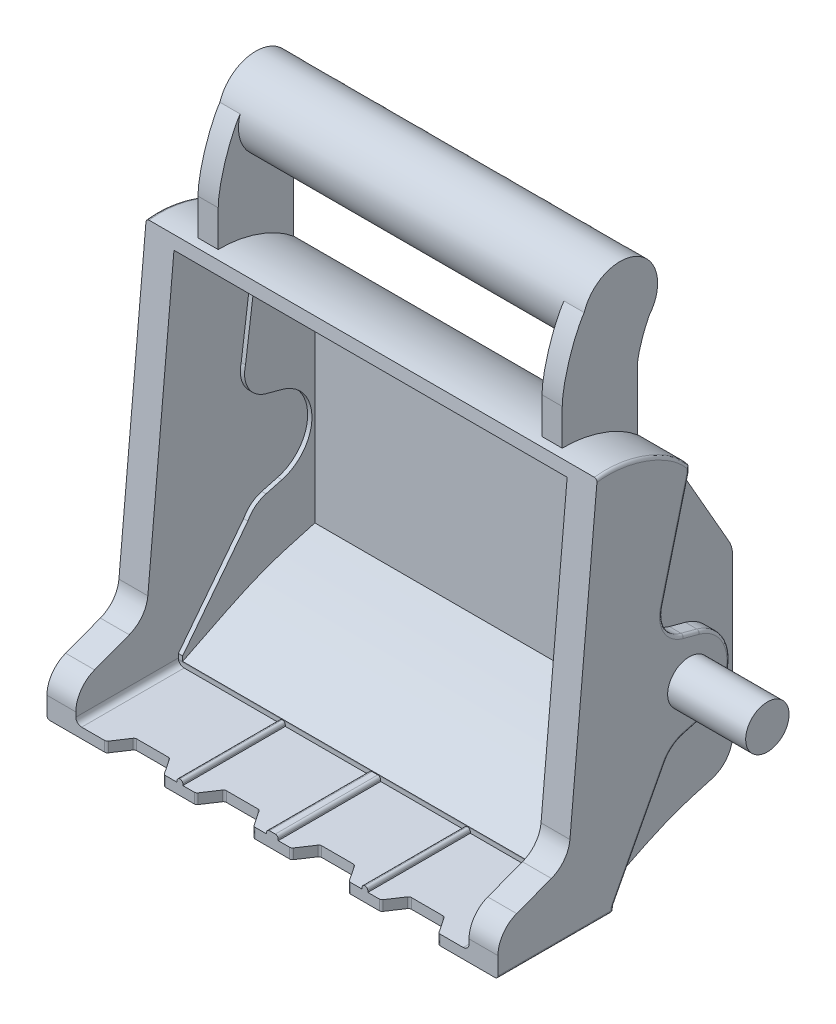
SolidWorks part; units mm, degrees
note: The reader was unsure of these and kept them because the rebuilt part matched: shared geometry of "Sketch1<8>", "Sketch6<3>", "Sketch10<4>", "Sketch10<5>", "Sketch11<4>".
material "PBT General Purpose"
ref_plane "Front Plane" through (0, 0, 0) normal (0, 0, 1) x (1, 0, 0)
ref_plane "Top Plane" through (0, 0, 0) normal (0, 1, 0) x (1, 0, 0)
ref_plane "Right Plane" through (0, 0, 0) normal (1, 0, 0) x (0, 0, -1)
sketch "Sketch1" plane through (0, 0, 0) normal (1, 0, 0) x (0, 0, -1)
  line L0 (0, 0) -> (-4.7154, -51.6541)
  line L1 (-7.9295, -55.8776) -> (-13.9281, -58.1411)
  line L2 (-17.1629, -62.8191) -> (-17.1629, -66.3617)
  line L3 (-17.1629, -66.3617) -> (2.8371, -66.3617)
  line L4 (2.8371, -66.3617) -> (2.9283, -65.3617)
  line L5 (25.9283, -56.3617) -> (25.9283, -24.3617)
  line L6 (25.9283, -24.3617) -> (16, -7)
  line L7 (16, -7) -> (16, -6)
  line L8 (2.2931, -2.38) -> (-2.2257, -51.8814)
  line L9 (-7.0469, -58.2167) -> (-13.0455, -60.4801)
  line L10 (-14.6629, -62.8191) -> (-14.6629, -63.8617)
  line L11 (-14.6629, -63.8617) -> (0.5549, -63.8617)
  line L12 (0.5549, -63.8617) -> (0.5649, -63.7517)
  line L13 (23.4283, -54.4401) -> (23.4283, -25.026)
  line L14 (23.4283, -25.026) -> (13.5, -7.6643)
  line L15 (13.5, -7.6643) -> (13.5, -6.9194)
  line L16 (-14.6629, -63.8617) -> (-17.1629, -63.8617)
  line L17 (2.2931, -2.38) -> (-0.1965, -2.1528)
  arc A0 (-4.7154, -51.6541) -> (-7.9295, -55.8776) centre (-9.6947, -51.1996) cw
  arc A1 (-13.9281, -58.1411) -> (-17.1629, -62.8191) centre (-12.1629, -62.8191) ccw
  arc A2 (-2.2257, -51.8814) -> (-7.0469, -58.2167) centre (-9.6947, -51.1996) cw
  arc A3 (-13.0455, -60.4801) -> (-14.6629, -62.8191) centre (-12.1629, -62.8191) ccw
  conic Q0 (2.9283, -65.3617) -> (25.9283, -56.3617) control (15.18, -59.202) rho 0.727082
  conic Q1 (16, -6) -> (0, 0) control (10.3278, 1.4347) rho 0.401111
  spline S0 degree 1 poles (13.5, -6.9194) (2.2931, -2.38) knots 0 0 1 1 construction
  spline S1 degree 1 poles (0.5649, -63.7517) (23.4283, -54.4401) knots 0 0 1 1 construction
  spline S2 degree 3 poles (13.5, -6.9194) (13.3729, -6.786) (13.1202, -6.5368) (12.5037, -5.9951) (11.5779, -5.3085) (10.2261, -4.5064) (8.6893, -3.7839) (7.04, -3.1852) (5.3626, -2.7418) (4.0174, -2.513) (3.0001, -2.4115) (2.5324, -2.3868) (2.2931, -2.38) knots 0.079459 0.079459 0.079459 0.079459 0.127453 0.175447 0.271436 0.367424 0.463412 0.5594 0.655388 0.751376 0.79937 0.847364 0.847364 0.847364 0.847364
  spline S3 degree 3 poles (0.5649, -63.7517) (1.2219, -63.4214) (2.6157, -62.7202) (4.2287, -61.9132) (5.5628, -61.2497) (7.0471, -60.5169) (8.5038, -59.8072) (9.873, -59.1546) (11.0033, -58.6305) (11.9816, -58.1918) (12.8652, -57.8113) (13.9719, -57.3563) (15.0367, -56.9517) (16.1815, -56.5528) (17.1182, -56.2449) (18.185, -55.9129) (19.2467, -55.5988) (20.2667, -55.3074) (21.1416, -55.0623) (21.9972, -54.8271) (22.7694, -54.6174) (23.2135, -54.4978) (23.4283, -54.4401) knots -0.019002 -0.019002 -0.019002 -0.019002 0.011686 0.042374 0.073062 0.10375 0.165125 0.226501 0.287877 0.349253 0.410629 0.472005 0.594757 0.656133 0.717509 0.778885 0.84026 0.870948 0.901636 0.932324 0.947668 0.963012 0.963012 0.963012 0.963012
  point P19 (-5, -54.7723)
  point P24 (-17.1629, -59.3617)
  dimension "D14" = 5
  dimension "D15" = 5
  dimension "D1" = 55
  dimension "D2" = 13
  dimension "D3" = 7
  dimension "D4" = 20
  dimension "D5" = 32
  dimension "D6" = 20
  dimension "D7" = 23
  dimension "D8" = 9
  dimension "D9" = 5
  dimension "D10" = 16
  dimension "D11" = 1
  dimension "D12" = 1
  dimension "D13" = 6
  dimension "D16" = 8.9337
  dimension "D17" = 10.3278
  dimension "D18" = 14.9749
  dimension "D19" = 15.18
  dimension "D20" = 1.4347
  dimension "D21" = 59.202
  dimension "D22" = 2.5
extrude "Boss-Extrude3" add sketch "Sketch1" against normal blind 36.5 contours S3 L12 L11 L16 L2 L3 L4 Q0 L5 L6 L7 Q1 L0 L17 S2 L15 L14 L13
extrude "Boss-Extrude4" add sketch "Sketch1<8>" against normal blind 2.5 contours L12 S3 L13 L14 L15 S2 L8 A2 L9 A3 L10 L11 | A3 L9 A2 L8 L17 L0 A0 L1 A1 L2 L16 L10
sketch "Sketch1<8>" plane through (0, 0, 0) normal (1, 0, 0) x (0, 0, -1) same geometry as "Sketch1"
sketch "Sketch6" plane through (0, 0, 0) normal (1, 0, 0) x (0, 0, -1)
  line L0 (16, -7) -> (11.4333, -24.7883)
  line L1 (17.7401, -31.6002) -> (14.9822, -30.8612)
  line L3 (17.7401, -45.1232) -> (14.9822, -45.8621)
  line L4 (11.8492, -48.3678) -> (2.9283, -65.3617)
  line L5 (25.9283, -56.3617) -> (25.9283, -24.3617) construction
  line L6 (2.8371, -66.3617) -> (2.9283, -65.3617) construction
  line L7 (-17.1629, -66.3617) -> (2.8371, -66.3617) construction
  line L8 (-17.1629, -62.8191) -> (-17.1629, -66.3617) construction
  line L9 (-7.9295, -55.8776) -> (-13.9281, -58.1411) construction
  line L10 (0, 0) -> (-4.7154, -51.6541) construction
  line L11 (16, -7) -> (16, -6) construction
  line L12 (2.8371, -66.3617) -> (2.9283, -65.3617)
  line L13 (-17.1629, -66.3617) -> (2.8371, -66.3617)
  line L14 (-17.1629, -62.8191) -> (-17.1629, -66.3617)
  line L15 (-7.9295, -55.8776) -> (-13.9281, -58.1411)
  line L16 (0, 0) -> (-4.7154, -51.6541)
  line L17 (16, -7) -> (16, -6)
  line L18 (1.3193, -27.2003) -> (1.3193, -49.5231)
  circle A1 centre (15.9283, -38.3617) radius 3.75
  arc A2 (17.7401, -31.6002) -> (17.7401, -45.1232) centre (15.9283, -38.3617) cw
  arc A3 (-13.9281, -58.1411) -> (-17.1629, -62.8191) centre (-12.1629, -62.8191) ccw construction
  arc A4 (-7.9295, -55.8776) -> (-4.7154, -51.6541) centre (-9.6947, -51.1996) ccw construction
  arc A5 (-13.9281, -58.1411) -> (-17.1629, -62.8191) centre (-12.1629, -62.8191) ccw
  arc A6 (-7.9295, -55.8776) -> (-4.7154, -51.6541) centre (-9.6947, -51.1996) ccw
  arc A7 (14.9822, -45.8621) -> (11.8492, -48.3678) centre (16.2763, -50.6918) ccw
  arc A8 (11.4333, -24.7883) -> (14.9822, -30.8612) centre (16.2763, -26.0316) ccw
  spline S0 degree 2 poles (16, -6) (10.3278, 1.4347) (0, 0) knots 0 0 0 1 1 1 weights 1 0.66976 1 construction
  spline S1 degree 2 poles (16, -6) (10.3278, 1.4347) (0, 0) knots 0 0 0 1 1 1 weights 1 0.66976 1
  point P6 (22.9283, -38.3617)
  line M5 (0, 0) -> (-4.7154, -51.6541)
  arc M6 (-4.7154, -51.6541) -> (-7.9295, -55.8776) centre (-9.6947, -51.1996) cw
  line M7 (-7.9295, -55.8776) -> (-13.9281, -58.1411)
  arc M8 (-13.9281, -58.1411) -> (-17.1629, -62.8191) centre (-12.1629, -62.8191) ccw
  line M9 (-17.1629, -62.8191) -> (-17.1629, -66.3617)
  line M10 (-17.1629, -66.3617) -> (2.8371, -66.3617)
  line M11 (2.8371, -66.3617) -> (2.9283, -65.3617)
  line M15 (16, -7) -> (16, -6)
  spline M16 degree 2 poles (16, -6) (10.3278, 1.4347) (0, 0) knots 0 0 0 1 1 1 weights 1 0.66976 1
  dimension "D1" = 7.5
  dimension "D5" = 150
  dimension "D2" = 7
  dimension "D7" = 5
  dimension "D3" = 18
  dimension "D4" = 10
  dimension "D6" = 18.4823
  dimension "D8" = 28.5963
  dimension "D9" = 16.8386
  dimension "D10" = 39.1614
extrude "Boss-Extrude5" add sketch "Sketch6" along normal blind 16 contours A1
extrude "Boss-Extrude6" add sketch "Sketch6<3>" along normal blind 2.5 contours L18 L1 L0 L4 L3 M15 M16 M5 M6 M7 M8 M9 M10 M11 | A2 L1 L18 L3 A1
sketch "Sketch6<3>" plane through (0, 0, 0) normal (1, 0, 0) x (0, 0, -1) same geometry as "Sketch6"
sketch "Sketch9" plane through (-2.5, 0, 0) normal (-1, 0, 0) x (0, 0, 1)
  line L0 (-2.2931, -2.38) -> (0.1965, -2.1528) construction
  line L1 (-2.2931, -2.38) -> (2.2257, -51.8814) construction
  line L2 (7.0469, -58.2167) -> (13.0455, -60.4801) construction
  line L3 (14.6629, -62.8191) -> (14.6629, -63.8617) construction
  line L4 (14.6629, -63.8617) -> (-0.5549, -63.8617) construction
  line L5 (-0.5549, -63.8617) -> (-0.5649, -63.7517) construction
  line L6 (-23.4283, -54.4401) -> (-23.4283, -25.026) construction
  line L7 (-23.4283, -25.026) -> (-13.5, -7.6643) construction
  line L8 (-13.5, -7.6643) -> (-13.5, -6.9194) construction
  line L9 (-0.5649, -63.7517) -> (-0.5549, -63.8617)
  line L10 (-0.5549, -63.8617) -> (17.1629, -63.8617)
  line L11 (17.1629, -63.8617) -> (17.1629, -62.8191)
  line L12 (13.9281, -58.1411) -> (7.9295, -55.8776)
  line L13 (4.7154, -51.6541) -> (0.1965, -2.1528)
  line L14 (0.1965, -2.1528) -> (-2.2931, -2.38)
  line L15 (-13.5, -6.9194) -> (-13.5, -7.6643)
  line L16 (-13.5, -7.6643) -> (-23.4283, -25.026)
  line L17 (-23.4283, -25.026) -> (-23.4283, -54.4401)
  line L18 (-0.5649, -63.7517) -> (-0.5549, -63.8617)
  line L19 (-0.5549, -63.8617) -> (17.1629, -63.8617)
  line L20 (17.1629, -63.8617) -> (17.1629, -62.8191)
  line L21 (13.9281, -58.1411) -> (7.9295, -55.8776)
  line L22 (4.7154, -51.6541) -> (0.1965, -2.1528)
  line L23 (0.1965, -2.1528) -> (-2.2931, -2.38)
  line L24 (-13.5, -6.9194) -> (-13.5, -7.6643)
  line L25 (-13.5, -7.6643) -> (-23.4283, -25.026)
  line L26 (-23.4283, -25.026) -> (-23.4283, -54.4401)
  line L27 (14.6629, -63.8617) -> (17.1629, -63.8617) construction
  line L28 (0, 0) -> (4.7154, -51.6541) construction
  line L29 (-16, -7) -> (-16, -6) construction
  line L30 (-25.9283, -24.3617) -> (-16, -7) construction
  line L31 (-25.9283, -56.3617) -> (-25.9283, -24.3617) construction
  line L32 (-2.8371, -66.3617) -> (-2.9283, -65.3617) construction
  line L33 (17.1629, -66.3617) -> (-2.8371, -66.3617) construction
  line L34 (17.1629, -62.8191) -> (17.1629, -66.3617) construction
  line L35 (7.9295, -55.8776) -> (13.9281, -58.1411) construction
  line L36 (-2.2931, -2.38) -> (0.1965, -2.1528)
  line L37 (-2.2931, -2.38) -> (2.2257, -51.8814)
  line L38 (7.0469, -58.2167) -> (13.0455, -60.4801)
  line L39 (14.6629, -62.8191) -> (14.6629, -63.8617)
  line L40 (14.6629, -63.8617) -> (-0.5549, -63.8617)
  line L41 (-0.5549, -63.8617) -> (-0.5649, -63.7517)
  line L42 (-23.4283, -54.4401) -> (-23.4283, -25.026)
  line L43 (-23.4283, -25.026) -> (-13.5, -7.6643)
  line L44 (-13.5, -7.6643) -> (-13.5, -6.9194)
  line L45 (14.6629, -63.8617) -> (17.1629, -63.8617)
  line L46 (0, 0) -> (4.7154, -51.6541)
  line L47 (-16, -7) -> (-16, -6)
  line L48 (-25.9283, -24.3617) -> (-16, -7)
  line L49 (-25.9283, -56.3617) -> (-25.9283, -24.3617)
  line L50 (-2.8371, -66.3617) -> (-2.9283, -65.3617)
  line L51 (17.1629, -66.3617) -> (-2.8371, -66.3617)
  line L52 (17.1629, -62.8191) -> (17.1629, -66.3617)
  line L53 (7.9295, -55.8776) -> (13.9281, -58.1411)
  line L54 (-0.1707, -63.1217) -> (-0.1707, -63.1217)
  line L55 (-0.1707, -63.1217) -> (16.4229, -63.1217)
  line L56 (16.4229, -63.1217) -> (16.4229, -62.8191)
  line L57 (13.6669, -58.8334) -> (7.6682, -56.57)
  line L58 (3.9784, -51.7214) -> (-0.4731, -2.957)
  line L59 (-0.4731, -2.957) -> (-2.249, -3.1191)
  line L60 (-12.76, -7.2231) -> (-12.76, -7.861)
  line L61 (-12.76, -7.861) -> (-22.6883, -25.2227)
  line L62 (-22.6883, -25.2227) -> (-22.6883, -53.873)
  line L63 (-13.5, -7.6643) -> (-13.5, -9.155)
  line L64 (-0.5649, -63.7517) -> (-0.5649, -62.9235)
  line L65 (-1.3193, -27.2003) -> (-1.3193, -49.5231) construction
  line L66 (-1.3193, -27.2003) -> (-1.3193, -49.5231)
  line L67 (-11.4333, -24.7883) -> (-13.5, -9.155)
  line L68 (-11.8492, -48.3678) -> (-0.5649, -62.9235)
  line L75 (-16, -6) -> (-16, -7)
  line L76 (-16, -7) -> (-11.4333, -24.7883)
  line L77 (-14.9822, -30.8612) -> (-17.7401, -31.6002)
  line L78 (-17.7401, -45.1232) -> (-14.9822, -45.8621)
  line L79 (-11.8492, -48.3678) -> (-2.9283, -65.3617)
  line L80 (-2.9283, -65.3617) -> (-2.8371, -66.3617)
  line L81 (-2.8371, -66.3617) -> (17.1629, -66.3617)
  line L82 (17.1629, -66.3617) -> (17.1629, -62.8191)
  line L83 (13.9281, -58.1411) -> (7.9295, -55.8776)
  line L84 (4.7154, -51.6541) -> (0, 0)
  line L85 (-16, -6) -> (-16, -7)
  line L87 (-14.9822, -30.8612) -> (-17.7401, -31.6002)
  line L88 (-17.7401, -45.1232) -> (-14.9822, -45.8621)
  line L90 (-2.9283, -65.3617) -> (-2.8371, -66.3617)
  line L91 (-2.8371, -66.3617) -> (17.1629, -66.3617)
  line L92 (17.1629, -66.3617) -> (17.1629, -62.8191)
  line L93 (13.9281, -58.1411) -> (7.9295, -55.8776)
  line L94 (4.7154, -51.6541) -> (0, 0)
  arc A0 (2.2257, -51.8814) -> (7.0469, -58.2167) centre (9.6947, -51.1996) ccw construction
  arc A1 (14.6629, -62.8191) -> (13.0455, -60.4801) centre (12.1629, -62.8191) ccw construction
  arc A2 (17.1629, -62.8191) -> (13.9281, -58.1411) centre (12.1629, -62.8191) ccw
  arc A3 (4.7154, -51.6541) -> (7.9295, -55.8776) centre (9.6947, -51.1996) ccw
  arc A4 (17.1629, -62.8191) -> (13.9281, -58.1411) centre (12.1629, -62.8191) ccw
  arc A5 (4.7154, -51.6541) -> (7.9295, -55.8776) centre (9.6947, -51.1996) ccw
  arc A6 (17.1629, -62.8191) -> (13.9281, -58.1411) centre (12.1629, -62.8191) ccw construction
  arc A7 (4.7154, -51.6541) -> (7.9295, -55.8776) centre (9.6947, -51.1996) ccw construction
  arc A8 (2.2257, -51.8814) -> (7.0469, -58.2167) centre (9.6947, -51.1996) ccw
  arc A9 (14.6629, -62.8191) -> (13.0455, -60.4801) centre (12.1629, -62.8191) ccw
  arc A10 (17.1629, -62.8191) -> (13.9281, -58.1411) centre (12.1629, -62.8191) ccw
  arc A11 (4.7154, -51.6541) -> (7.9295, -55.8776) centre (9.6947, -51.1996) ccw
  arc A12 (16.4229, -62.8191) -> (13.6669, -58.8334) centre (12.1629, -62.8191) ccw
  arc A13 (3.9784, -51.7214) -> (7.6682, -56.57) centre (9.6947, -51.1996) ccw
  circle A15 centre (-15.9283, -38.3617) radius 3.75
  circle A16 centre (-15.9283, -38.3617) radius 3.75
  arc A21 (-14.9822, -30.8612) -> (-11.4333, -24.7883) centre (-16.2763, -26.0316) ccw
  arc A22 (-17.7401, -31.6002) -> (-17.7401, -45.1232) centre (-15.9283, -38.3617) ccw
  arc A23 (-11.8492, -48.3678) -> (-14.9822, -45.8621) centre (-16.2763, -50.6918) ccw
  arc A24 (17.1629, -62.8191) -> (13.9281, -58.1411) centre (12.1629, -62.8191) ccw
  arc A25 (4.7154, -51.6541) -> (7.9295, -55.8776) centre (9.6947, -51.1996) ccw
  arc A26 (-14.9822, -30.8612) -> (-11.4333, -24.7883) centre (-16.2763, -26.0316) ccw
  arc A27 (-17.7401, -31.6002) -> (-17.7401, -45.1232) centre (-15.9283, -38.3617) ccw
  arc A28 (-11.8492, -48.3678) -> (-14.9822, -45.8621) centre (-16.2763, -50.6918) ccw
  arc A29 (17.1629, -62.8191) -> (13.9281, -58.1411) centre (12.1629, -62.8191) ccw
  arc A30 (4.7154, -51.6541) -> (7.9295, -55.8776) centre (9.6947, -51.1996) ccw
  spline S0 degree 3 poles (-1781.4369, 846.3816) (80.7181, -105.0875) (10.5569, -69.3107) (-4.2287, -61.9132) (-5.5628, -61.2497) (-7.0471, -60.5169) (-8.5038, -59.8072) (-9.873, -59.1546) (-11.0033, -58.6305) (-11.9816, -58.1918) (-12.8652, -57.8113) (-13.9719, -57.3563) (-15.0367, -56.9517) (-16.1815, -56.5528) (-17.1182, -56.2449) (-18.185, -55.9129) (-19.2467, -55.5988) (-20.2667, -55.3074) (-21.1416, -55.0623) (-21.9972, -54.8271) (-31.3701, -52.282) (-71.7819, -41.8206) (1907.1824, -576.0612) knots -0.770858 -0.770858 -0.770858 -0.770858 0.011686 0.042374 0.073062 0.10375 0.165125 0.226501 0.287877 0.349253 0.410629 0.472005 0.594757 0.656133 0.717509 0.778885 0.84026 0.870948 0.901636 0.932324 0.947668 1.646622 1.646622 1.646622 1.646622 only from (-0.5649, -63.7517) to (-23.4283, -54.4401) construction
  spline S1 degree 3 poles (-1424.0297, -1424.6145) (3.9839, -6.8836) (-20.1442, -12.7085) (-12.5037, -5.9951) (-11.5779, -5.3085) (-10.2261, -4.5064) (-8.6893, -3.7839) (-7.04, -3.1852) (-5.3626, -2.7418) (-4.0174, -2.513) (9.6179, -1.1527) (-4.5748, -17.202) (1996.1326, 75.175) knots -2.107535 -2.107535 -2.107535 -2.107535 0.127453 0.175447 0.271436 0.367424 0.463412 0.5594 0.655388 0.751376 0.79937 3.22846 3.22846 3.22846 3.22846 only from (-13.5, -6.9194) to (-2.2931, -2.38) construction
  spline S2 degree 3 poles (2994.9331, 122.328) (-9.1417, -22.095) (11.4765, -0.9672) (-4.0174, -2.513) (-5.3626, -2.7418) (-7.04, -3.1852) (-8.6893, -3.7839) (-10.2261, -4.5064) (-11.5779, -5.3085) (-12.5037, -5.9951) (-21.1761, -13.6152) (11.3981, -5.0011) (-2134.27, -2128.5336) knots -2.652374 -2.652374 -2.652374 -2.652374 0.127453 0.175447 0.271436 0.367424 0.463412 0.5594 0.655388 0.751376 0.79937 3.355645 3.355645 3.355645 3.355645 only from (-2.2931, -2.38) to (-13.5, -6.9194)
  spline S3 degree 3 poles (2872.6583, -836.672) (-83.5567, -38.7746) (-32.6126, -51.9446) (-21.9972, -54.8271) (-21.1416, -55.0623) (-20.2667, -55.3074) (-19.2467, -55.5988) (-18.185, -55.9129) (-17.1182, -56.2449) (-16.1815, -56.5528) (-15.0367, -56.9517) (-13.9719, -57.3563) (-12.8652, -57.8113) (-11.9816, -58.1918) (-11.0033, -58.6305) (-9.873, -59.1546) (-8.5038, -59.8072) (-7.0471, -60.5169) (-5.5628, -61.2497) (-4.2287, -61.9132) (12.4565, -70.2611) (100.4196, -115.1362) (-2671.8187, 1301.3187) knots -0.801367 -0.801367 -0.801367 -0.801367 -0.003658 0.011686 0.042374 0.073062 0.10375 0.165125 0.226501 0.287877 0.349253 0.472005 0.533381 0.594757 0.656133 0.717509 0.778885 0.84026 0.870948 0.901636 0.932324 1.823287 1.823287 1.823287 1.823287 only from (-23.4283, -54.4401) to (-0.5649, -63.7517)
  spline S4 degree 3 poles (-2.2931, -2.38) (-2.5324, -2.3868) (-3.0001, -2.4115) (-4.0174, -2.513) (-5.3626, -2.7418) (-7.04, -3.1852) (-8.6893, -3.7839) (-10.2261, -4.5064) (-11.5779, -5.3085) (-12.5037, -5.9951) (-13.1202, -6.5368) (-13.3729, -6.786) (-13.5, -6.9194) knots 0.079459 0.079459 0.079459 0.079459 0.127453 0.175447 0.271436 0.367424 0.463412 0.5594 0.655388 0.751376 0.79937 0.847364 0.847364 0.847364 0.847364
  spline S5 degree 3 poles (-23.4283, -54.4401) (-23.2135, -54.4978) (-22.7694, -54.6174) (-21.9972, -54.8271) (-21.1416, -55.0623) (-20.2667, -55.3074) (-19.2467, -55.5988) (-18.185, -55.9129) (-17.1182, -56.2449) (-16.1815, -56.5528) (-15.0367, -56.9517) (-13.9719, -57.3563) (-12.8652, -57.8113) (-11.9816, -58.1918) (-11.0033, -58.6305) (-9.873, -59.1546) (-8.5038, -59.8072) (-7.0471, -60.5169) (-5.5628, -61.2497) (-4.2287, -61.9132) (-2.6157, -62.7202) (-1.2219, -63.4214) (-0.5649, -63.7517) knots -0.019002 -0.019002 -0.019002 -0.019002 -0.003658 0.011686 0.042374 0.073062 0.10375 0.165125 0.226501 0.287877 0.349253 0.472005 0.533381 0.594757 0.656133 0.717509 0.778885 0.84026 0.870948 0.901636 0.932324 0.963012 0.963012 0.963012 0.963012
  spline S6 degree 2 poles (-16, -6) (-10.3278, 1.4347) (0, 0) knots 0 0 0 1 1 1 weights 1 0.66976 1 construction
  spline S7 degree 2 poles (-2.9283, -65.3617) (-15.18, -59.202) (-25.9283, -56.3617) knots 0 0 0 1 1 1 weights 1 2.664109 1 construction
  spline S8 degree 3 poles (-0.5649, -63.7517) (-1.2219, -63.4214) (-2.6157, -62.7202) (-4.2287, -61.9132) (-5.5628, -61.2497) (-7.0471, -60.5169) (-8.5038, -59.8072) (-9.873, -59.1546) (-11.0033, -58.6305) (-11.9816, -58.1918) (-12.8652, -57.8113) (-13.9719, -57.3563) (-15.0367, -56.9517) (-16.1815, -56.5528) (-17.1182, -56.2449) (-18.185, -55.9129) (-19.2467, -55.5988) (-20.2667, -55.3074) (-21.1416, -55.0623) (-21.9972, -54.8271) (-22.7694, -54.6174) (-23.2135, -54.4978) (-23.4283, -54.4401) knots -0.019002 -0.019002 -0.019002 -0.019002 0.011686 0.042374 0.073062 0.10375 0.165125 0.226501 0.287877 0.349253 0.410629 0.472005 0.594757 0.656133 0.717509 0.778885 0.84026 0.870948 0.901636 0.932324 0.947668 0.963012 0.963012 0.963012 0.963012
  spline S9 degree 3 poles (-13.5, -6.9194) (-13.3729, -6.786) (-13.1202, -6.5368) (-12.5037, -5.9951) (-11.5779, -5.3085) (-10.2261, -4.5064) (-8.6893, -3.7839) (-7.04, -3.1852) (-5.3626, -2.7418) (-4.0174, -2.513) (-3.0001, -2.4115) (-2.5324, -2.3868) (-2.2931, -2.38) knots 0.079459 0.079459 0.079459 0.079459 0.127453 0.175447 0.271436 0.367424 0.463412 0.5594 0.655388 0.751376 0.79937 0.847364 0.847364 0.847364 0.847364
  spline S10 degree 2 poles (-16, -6) (-10.3278, 1.4347) (0, 0) knots 0 0 0 1 1 1 weights 1 0.66976 1
  spline S11 degree 2 poles (-2.9283, -65.3617) (-15.18, -59.202) (-25.9283, -56.3617) knots 0 0 0 1 1 1 weights 1 2.664109 1
  spline S12 degree 1 poles (-2.249, -3.1191) (-12.76, -7.2231) knots 0 0 1 1 construction
  spline S13 degree 1 poles (-22.6883, -53.873) (-0.1707, -63.1217) knots 0 0 1 1 construction
  spline S14 degree 3 poles (-2.249, -3.1191) (-2.4685, -3.1253) (-2.8978, -3.1464) (-3.8302, -3.2361) (-5.0709, -3.4389) (-6.6262, -3.8351) (-8.1672, -4.3733) (-9.6145, -5.0258) (-10.9027, -5.7564) (-11.7899, -6.3791) (-12.3935, -6.879) (-12.6364, -7.1025) (-12.76, -7.2231) knots 0.077909 0.077909 0.077909 0.077909 0.124261 0.170612 0.263315 0.356019 0.448722 0.541425 0.634128 0.726832 0.773183 0.819535 0.819535 0.819535 0.819535
  spline S15 degree 3 poles (-22.6883, -53.873) (-22.4912, -53.9263) (-22.0833, -54.0368) (-21.3766, -54.23) (-20.5777, -54.4512) (-19.7582, -54.6825) (-18.7902, -54.9613) (-17.7715, -55.2654) (-16.7325, -55.5915) (-15.8102, -55.8975) (-14.6728, -56.2971) (-13.6041, -56.706) (-12.4899, -57.1665) (-11.5996, -57.5516) (-10.6139, -57.9948) (-9.4761, -58.5236) (-8.0996, -59.1807) (-6.6379, -59.8934) (-5.1494, -60.6287) (-3.8171, -61.2916) (-2.3325, -62.0347) (-1.0917, -62.6586) (-0.4323, -62.9902) (-0.2688, -63.0723) (-0.1707, -63.1217) knots -0.006035 -0.006035 -0.006035 -0.006035 0.009121 0.024277 0.05459 0.084903 0.115216 0.175842 0.236467 0.297093 0.357718 0.47897 0.539595 0.600221 0.660847 0.721472 0.782098 0.842723 0.873036 0.903349 0.933662 0.956356 0.959404 0.963975 0.963975 0.963975 0.963975
  spline S17 degree 2 poles (0, 0) (-10.3278, 1.4347) (-16, -6) knots 0 0 0 1 1 1 weights 1 0.66976 1
  spline S18 degree 2 poles (0, 0) (-10.3278, 1.4347) (-16, -6) knots 0 0 0 1 1 1 weights 1 0.66976 1
  line M24 (-13.5, -7.6643) -> (-23.4283, -25.026)
  line M25 (-23.4283, -25.026) -> (-23.4283, -54.4401)
  spline M26 degree 3 poles (-0.5649, -63.7517) (-1.2219, -63.4214) (-2.6157, -62.7202) (-4.2287, -61.9132) (-5.5628, -61.2497) (-7.0471, -60.5169) (-8.5038, -59.8072) (-9.873, -59.1546) (-11.0033, -58.6305) (-11.9816, -58.1918) (-12.8652, -57.8113) (-13.9719, -57.3563) (-15.0367, -56.9517) (-16.1815, -56.5528) (-17.1182, -56.2449) (-18.185, -55.9129) (-19.2467, -55.5988) (-20.2667, -55.3074) (-21.1416, -55.0623) (-21.9972, -54.8271) (-22.7694, -54.6174) (-23.2135, -54.4978) (-23.4283, -54.4401) knots -0.019002 -0.019002 -0.019002 -0.019002 0.011686 0.042374 0.073062 0.10375 0.165125 0.226501 0.287877 0.349253 0.410629 0.472005 0.594757 0.656133 0.717509 0.778885 0.84026 0.870948 0.901636 0.932324 0.947668 0.963012 0.963012 0.963012 0.963012
  dimension "D1" = 0
  dimension "D2" = 0.74
  dimension "D3" = 0
  dimension "D4" = 0
extrude "Boss-Extrude7" add sketch "Sketch9" along normal blind 0.74 contours A27 L87 A26 L67 L61 L62 | L62 S15 L68 A28 L88 A27 | S15 L62 A27 L61 L63 L64 M24 M25 M26
sketch "Sketch10" plane through (0, -63.8617, 0) normal (0, 1, 0) x (1, 0, 0)
  line L0 (-36.5, -17.1629) -> (-2.5, -17.1629) construction
  line L1 (-36.5, 0.5549) -> (-35.5, 0.5549)
  line L2 (-36.5, 0.5549) -> (-36.5, -17.1629)
  line L3 (-36.5, -17.1629) -> (-35.5, -17.1629)
  line L4 (-35.5, 0.5549) -> (-35.5, -17.1629)
  line L5 (-36.5, 0.5549) -> (-2.5, 0.5549) construction
  line L6 (-21, 0.5549) -> (-20, 0.5549)
  line L7 (-21, 0.5549) -> (-21, -17.1629)
  line L8 (-21, -17.1629) -> (-20, -17.1629)
  line L9 (-20, 0.5549) -> (-20, -17.1629)
  line L10 (-33.25, -17.1629) -> (-31.25, -14.1629)
  line L11 (-31.25, -14.1629) -> (-25.25, -14.1629)
  line L12 (-25.25, -14.1629) -> (-23.25, -17.1629)
  line L13 (-33.25, -17.1629) -> (-23.25, -17.1629)
  line L14 (-35.5, -17.1629) -> (-21, -17.1629)
  line L15 (-36.5, 0.5549) -> (-2.5, 0.5549)
  line L16 (-36.5, 0.5549) -> (-36.5, -17.1629)
  line L17 (-36.5, -17.1629) -> (-2.5, -17.1629)
  line L18 (-2.5, 0.5549) -> (-2.5, -17.1629)
  line L19 (-17.75, -17.1629) -> (-15.75, -14.1629)
  line L20 (-15.75, -14.1629) -> (-9.75, -14.1629)
  line L21 (-9.75, -14.1629) -> (-7.75, -17.1629)
  line L22 (-17.75, -17.1629) -> (-7.75, -17.1629)
  point P22 (-28.25, -17.1629)
  point P23 (-28.25, -17.1629)
  line M17 (-2.5, -17.1629) -> (-2.5, 0.5549)
  line M18 (-2.5, 0.5549) -> (-36.5, 0.5549)
  line M19 (-36.5, 0.5549) -> (-36.5, -17.1629)
  line M20 (-36.5, -17.1629) -> (-2.5, -17.1629)
  dimension "D1" = 1
  dimension "D2" = 1
  dimension "D3" = 14.5
  dimension "D4" = 6
  dimension "D5" = 10
  dimension "D6" = 3
  dimension "D7" = 2
  dimension "D8" = 2.25
extrude "Cut-Extrude2" cut sketch "Sketch10" against normal blind 0.74 contours L4 M18 M19 M20 | L11 L12 L7 L4 L10 M20 M18 | L12 L11 L10 M20 | L9 L7 M18 M20 | L20 L21 L9 L19 M20 M17 M18 | L21 L20 L19 L17 | L2
extrude "Cut-Extrude3" cut sketch "Sketch10<4>" against normal through all contours L12 L11 L10 M20 | L21 L20 L19 L17
sketch "Sketch10<4>" plane through (0, -63.8617, 0) normal (0, 1, 0) x (1, 0, 0) same geometry as "Sketch10"
extrude "Boss-Extrude8" add sketch "Sketch10<5>" against normal up to surface (0.74 mm away) contours L4 M18 M19 M20 | L9 L7 M18 M20 up to face at (-20.1667, -64.6017, 13.21)
sketch "Sketch10<5>" plane through (0, -63.8617, 0) normal (0, 1, 0) x (1, 0, 0) same geometry as "Sketch10"
fillet "Fillet1" radius 5 2 edges at (-18.25, -56.3617, -25.9283) (-18.25, -24.3617, -25.9283)
fillet "Fillet2" radius 0.5 12 edges at (2.5, -28.5543, -11.9593) (2.5, -15.8941, -13.7167) (2.5, -56.8647, -7.3888) (2.5, -46.787, -13.1533) (2.5, -45.4927, -16.3611) (2.5, -38.3617, -22.9283) (2.5, -6.5, -16) (2.5, -66.3617, 7.1629) (2.5, -65.8617, -2.8827) (2.5, -31.2307, -16.3611) (-17, -66.3617, -2.8371)
fillet "Fillet3" radius 0.5 3 edges at (-35.5, -63.8617, 8.304) (-21, -63.8617, 8.304) (-20, -63.8617, 8.304)
fillet "Fillet4" radius 0.5 8 edges at (-7.75, -65.4817, 17.1629) (-9.75, -65.4817, 14.1629) (-15.75, -65.4817, 14.1629) (-17.75, -65.4817, 17.1629) (-23.25, -65.4817, 17.1629) (-33.25, -65.4817, 17.1629) (-31.25, -65.4817, 14.1629) (-25.25, -65.4817, 14.1629)
fillet "Fillet5" radius 1 1 edges at (-2.5, -64.6017, 8.304)
ref_plane "Plane2" through (-36.5, 0, 0) normal (-1, 0, 0) x (0, 0, 1)
ref_plane "Plane3" through (-5, 0, 0) normal (1, 0, 0) x (0, 0, -1)
sketch "Sketch11" plane through (-5, 0, 0) normal (1, 0, 0) x (0, 0, -1)
  line L0 (-0.0467, -0.5113) -> (1.4533, -0.5113)
  line L1 (1.4533, -0.5113) -> (1.4533, 6.3752)
  line L3 (14.4533, -6.4032) -> (14.4533, 6.3752)
  circle A0 centre (11.4533, 16.5968) radius 6.5
  conic Q0 (1.4533, -0.5113) -> (14.4533, -6.4032) control (8.4107, -2.448) rho 0.75
  conic Q1 (1.4533, 6.3752) -> (5.2485, 18.5335) control (1.4533, 13.0467) rho 0.377255
  conic Q2 (14.4533, 6.3752) -> (17.5116, 14.2415) control (15.025, 10.6806) rho 0.412762
  dimension "D3" = 13
  dimension "D1" = 1.5
  dimension "D2" = 13
  dimension "D4" = 23
  dimension "D5" = 10
  dimension "D6" = 1.4533
  dimension "D7" = 2.6351
  dimension "D8" = 5.2485
  dimension "D9" = 8.2964
  dimension "D10" = 8.4107
  dimension "D11" = 15.025
  dimension "D12" = 15.5872
  dimension "D13" = 17.5116
  dimension "D14" = 6.3752
  dimension "D15" = 6.3752
  dimension "D16" = 10.462
  dimension "D17" = 10.6806
  dimension "D18" = 12.6778
  dimension "D19" = 2.448
extrude "Boss-Extrude9" add sketch "Sketch11" against normal blind 3.5 contours L3 Q2 A0 Q1 L1 Q0
extrude "Boss-Extrude10" add sketch "Sketch11<4>" against normal up to surface (31.5 mm away) contours A0 up to plane "Plane2"
sketch "Sketch11<4>" plane through (-5, 0, 0) normal (1, 0, 0) x (0, 0, -1) same geometry as "Sketch11"
ref_plane "Plane4" through (0, 0, -17.9533) normal (0, 0, -1) x (-1, 0, 0)
sketch "Sketch13" plane through (0, 0, -17.9533) normal (0, 0, -1) x (-1, 0, 0)
  line L0 (8.5, 10.0968) -> (8.5, 18.5335) construction
  line L1 (8.5, 11.5968) -> (36.5, 11.5968)
  line L2 (8.5, 11.5968) -> (8.5, 21.5968)
  line L3 (8.5, 21.5968) -> (36.5, 21.5968)
  line L4 (36.5, 11.5968) -> (36.5, 21.5968)
  line L5 (36.5, 10.0968) -> (36.5, 23.0968) construction
  line L6 (8.5, 23.0968) -> (8.5, 10.0968)
  line L7 (36.5, 23.0968) -> (5, 23.0968) construction
  line L8 (15.625, 21.5968) -> (15.625, 17.0968)
  line L9 (8.5, 21.5968) -> (14.5, 21.5968)
  line L10 (8.5, 21.5968) -> (8.5, 17.0968)
  line L11 (8.5, 17.0968) -> (14.5, 17.0968)
  line L12 (14.5, 21.5968) -> (14.5, 17.0968)
  line L13 (15.625, 21.5968) -> (21.625, 21.5968)
  line L14 (21.625, 21.5968) -> (21.625, 17.0968)
  line L15 (15.625, 17.0968) -> (21.625, 17.0968)
  line L16 (22.75, 21.5968) -> (22.75, 17.0968)
  line L17 (22.75, 21.5968) -> (28.75, 21.5968)
  line L18 (28.75, 21.5968) -> (28.75, 17.0968)
  line L19 (22.75, 17.0968) -> (28.75, 17.0968)
  line L20 (29.875, 21.5968) -> (29.875, 17.0968)
  line L21 (29.875, 21.5968) -> (35.875, 21.5968)
  line L22 (35.875, 21.5968) -> (35.875, 17.0968)
  line L23 (29.875, 17.0968) -> (35.875, 17.0968)
  line L24 (15.625, 16.0968) -> (15.625, 11.5968)
  line L25 (15.625, 16.0968) -> (21.625, 16.0968)
  line L26 (21.625, 16.0968) -> (21.625, 11.5968)
  line L27 (15.625, 11.5968) -> (21.625, 11.5968)
  line L28 (22.75, 16.0968) -> (22.75, 11.5968)
  line L29 (22.75, 16.0968) -> (28.75, 16.0968)
  line L30 (28.75, 16.0968) -> (28.75, 11.5968)
  line L31 (22.75, 11.5968) -> (28.75, 11.5968)
  line L32 (29.875, 16.0968) -> (29.875, 11.5968)
  line L33 (29.875, 16.0968) -> (35.875, 16.0968)
  line L34 (35.875, 16.0968) -> (35.875, 11.5968)
  line L35 (29.875, 11.5968) -> (35.875, 11.5968)
  line L36 (8.5, 16.0968) -> (8.5, 11.5968)
  line L37 (8.5, 16.0968) -> (14.5, 16.0968)
  line L38 (14.5, 16.0968) -> (14.5, 11.5968)
  line L39 (8.5, 11.5968) -> (14.5, 11.5968)
  point P14 (8.5, 16.5968)
  point P15 (8.5, 16.5968)
  dimension "D1" = 10
  dimension "D2" = 4.5
  dimension "D3" = 6
  dimension "D6" = 15.625
  dimension "D7" = 15.625
  dimension "D8" = 1
  dimension "D4" = 4
  dimension "D5" = 2
extrude "Cut-Extrude5" cut sketch "Sketch13" against normal blind 10 contours L12 L3 L6 L11 | L8 L15 L14 L3 | L38 L37 L2 L1 | L26 L25 L24 L1 | L16 L19 L18 L3 | L30 L29 L28 L1 | L34 L33 L32 L1 | L20 L23 L22 L3
mirror "Mirror2" about plane through (-36.5, 0, 0) normal (-1, 0, 0) of bodies 119
